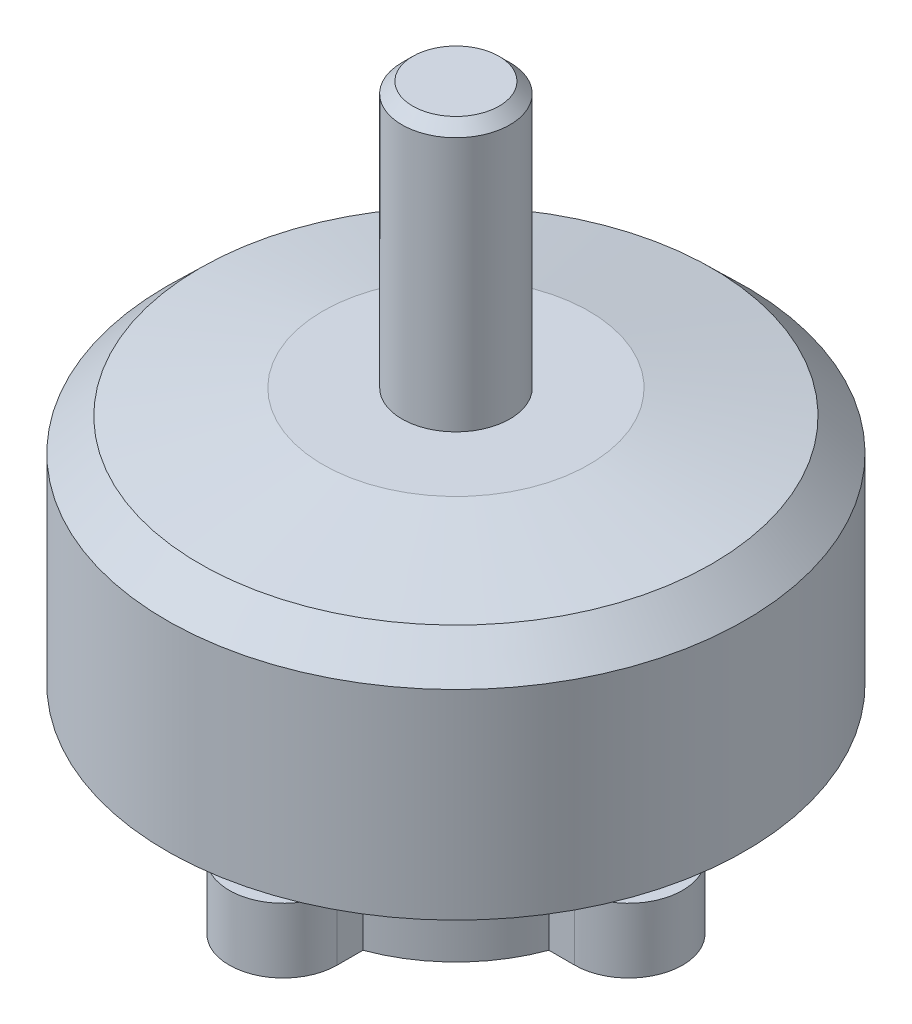
SolidWorks part; units mm, degrees
ref_plane "Спереди" through (0, 0, 0) normal (0, 0, 1) x (1, 0, 0)
ref_plane "Сверху" through (0, 0, 0) normal (0, 1, 0) x (1, 0, 0)
ref_plane "Справа" through (0, 0, 0) normal (1, 0, 0) x (0, 0, -1)
sketch "Эскиз1" plane through (0, 0, 0) normal (0, 1, 0) x (1, 0, 0)
  line L0 (0, 8) -> (0, 6) construction
  line L1 (2.5, 8) -> (2.5, 6)
  line L2 (-2.5, 8) -> (-2.5, 6)
  line L3 (8, 2.5) -> (6, 2.5)
  line L4 (8, -2.5) -> (6, -2.5)
  line L5 (8, 0) -> (6, 0) construction
  line L6 (2.5, -8) -> (2.5, -6)
  line L7 (-2.5, -8) -> (-2.5, -6)
  line L8 (0, -8) -> (0, -6) construction
  line L9 (-8, -2.5) -> (-6, -2.5)
  line L10 (-8, 2.5) -> (-6, 2.5)
  line L11 (-8, 0) -> (-6, 0) construction
  circle A0 centre (0, 0) radius 8 construction
  circle A1 centre (0, 8) radius 1.25
  circle A2 centre (8, 0) radius 1.25
  circle A3 centre (0, -8) radius 1.25
  circle A4 centre (-8, 0) radius 1.25
  circle A5 centre (0, 0) radius 6
  circle A6 centre (0, 0) radius 7.25
  arc A7 (2.5, 8) -> (-2.5, 8) centre (0, 8) ccw
  arc A8 (-2.5, 6) -> (2.5, 6) centre (0, 6) ccw
  arc A9 (8, -2.5) -> (8, 2.5) centre (8, 0) ccw
  arc A10 (6, 2.5) -> (6, -2.5) centre (6, 0) ccw
  arc A11 (-2.5, -8) -> (2.5, -8) centre (0, -8) ccw
  arc A12 (2.5, -6) -> (-2.5, -6) centre (0, -6) ccw
  arc A13 (-8, 2.5) -> (-8, -2.5) centre (-8, 0) ccw
  arc A14 (-6, -2.5) -> (-6, 2.5) centre (-6, 0) ccw
  point P13 (0, 7)
  point P23 (7, 0)
  point P30 (0, -7)
  point P37 (-7, 0)
  point P43 (0, 0)
  dimension "D1" = 16
  dimension "D2" = 2.5
  dimension "D3" = 12
  dimension "D4" = 14.5
  dimension "D5" = 2.5
  dimension "D6" = 4
extrude "Бобышка-Вытянуть1" add sketch "Эскиз1" along normal blind 3 contours A14 L9 A6 L7 A12 A5 | L10 A13 L9 A6 A4 | A5 A8 L1 A6 A1 L2 | L1 A7 L2 A6 A1 | A10 L3 A6 L1 A8 A5 | A14 A5 A8 L2 A6 L10 | L6 A12 A5 L7 A6 A3 | L9 A14 A5 L10 A6 A4 | L3 A10 A5 L4 A6 A2 | A12 L6 A6 L4 A10 A5 | L4 A9 L3 A6 A2 | L7 A11 L6 A6 A3 region at (2.4378, 0, -7.4027) region at (4.5855, 0, -4.5855) region at (0, 0, -6.3965) region at (6.3965, 0, 0) region at (7.4027, 0, -2.4378) region at (-4.5855, 0, -4.5855) region at (-7.0996, 0, -1.7504) region at (-6.3965, 0, 0) region at (4.5855, 0, 4.5855) region at (0, 0, 6.3965) region at (-4.5855, 0, 4.5855) region at (2.4378, 0, 7.4027)
cosmetic thread "Условное изображение резьбы1" parameters "D2"=3
cosmetic thread "Условное изображение резьбы2" parameters "D2"=3
cosmetic thread "Условное изображение резьбы3" parameters "D2"=3
cosmetic thread "Условное изображение резьбы4" parameters "D2"=3
sketch "Эскиз6" plane through (0, 0, 0) normal (0, 0, 1) x (1, 0, 0)
  line L0 (37.7821, 505.6995) -> (251.7821, 505.6995) construction
sketch "Эскиз2" plane through (0, 0, 0) normal (1, 0, 0) x (0, 0, -1)
  line L0 (6, 3) -> (4.2, 4.5)
  line L1 (6, 3) -> (-6, 3) construction
  line L2 (6.8053, 3) -> (2.5, 3) construction
  line L3 (4.2, 4.5) -> (0, 4.5)
  line L4 (0, 4.5) -> (0, 5.5)
  line L5 (0, 5.5) -> (3.8053, 5.5)
  line L6 (3.8053, 5.5) -> (6.8053, 3)
  line L7 (-6, 0) -> (6, 0) construction
  line L8 (6, 3) -> (6.8053, 3)
  dimension "D1" = 4.5
  dimension "D2" = 4.2
  dimension "D3" = 1
revolve "Повернуть1" add sketch "Эскиз2" angle 360 about L4
sketch "Эскиз3" plane through (0, 4.5, 0) normal (0, -1, 0) x (1, 0, 0)
  circle A0 centre (0, 0) radius 1.25
  dimension "D1" = 2.5
extrude "Вырез-Вытянуть1" cut sketch "Эскиз3" against normal through all
sketch "Эскиз4" plane through (0, 0, 2.5) normal (0, 0, 1) x (1, 0, 0)
  line L0 (8.0234, 3) -> (2.8689, 5.5)
  line L1 (9.25, 3) -> (6.7969, 3) construction
  line L2 (3.8053, 5.5) -> (-3.8053, 5.5) construction
  line L4 (6.8053, 3) -> (8.0234, 3)
  line L5 (6.8053, 3) -> (6.3295, 3)
  line L6 (6.3295, 3) -> (2.8689, 5.5)
extrude "Бобышка-Вытянуть2" add sketch "Эскиз4" against normal blind 0.75
mirror "Зеркальное отражение1" about plane through (0, 0, 0) normal (0, 0, 1) of "Бобышка-Вытянуть2"
pattern_circular "Круговой массив1" count 4 over 360 about axis through (0, 5.5, 0) along (0, -1, 0) of "Зеркальное отражение1"
sketch "Эскиз7" plane through (0, 0, 0) normal (0, 0, 1) x (1, 0, 0)
  line L0 (5.3632, 4.2902) -> (5.3632, 6.0305)
  line L1 (8.0234, 3) -> (2.8689, 5.5) construction
  line L2 (5.3632, 6.0305) -> (13.4, 6.0305)
  line L3 (13.4, 6.0305) -> (13.4, 15.2805)
  line L4 (13.4, 15.2805) -> (11.8618, 16.7778)
  line L5 (11.8618, 16.7778) -> (6.1633, 17.9076)
  line L6 (6.1633, 17.9076) -> (0, 17.9076)
  line L7 (0, 17.9076) -> (0, 4.2902)
  line L8 (0, 4.2902) -> (5.3632, 4.2902)
  dimension "D1" = 13.4
  dimension "D2" = 9.25
revolve "Повернуть3" add sketch "Эскиз7" angle 360 about L7
sketch "Эскиз8" plane through (0, 17.9076, 0) normal (0, 1, 0) x (1, 0, 0)
  circle A0 centre (0, 0) radius 2.5
  dimension "D1" = 5
extrude "Бобышка-Вытянуть3" add sketch "Эскиз8" along normal blind 12.3
chamfer "Фаска2" distance 0.5 angle 45 1 edges at (-2.5, 30.2076, 0)
chamfer "Фаска3" distance 0.5 angle 45 4 edges at (0, 0, -6.75) (8, 0, 1.25) (0, 0, 9.25) (-8, 0, 1.25)
